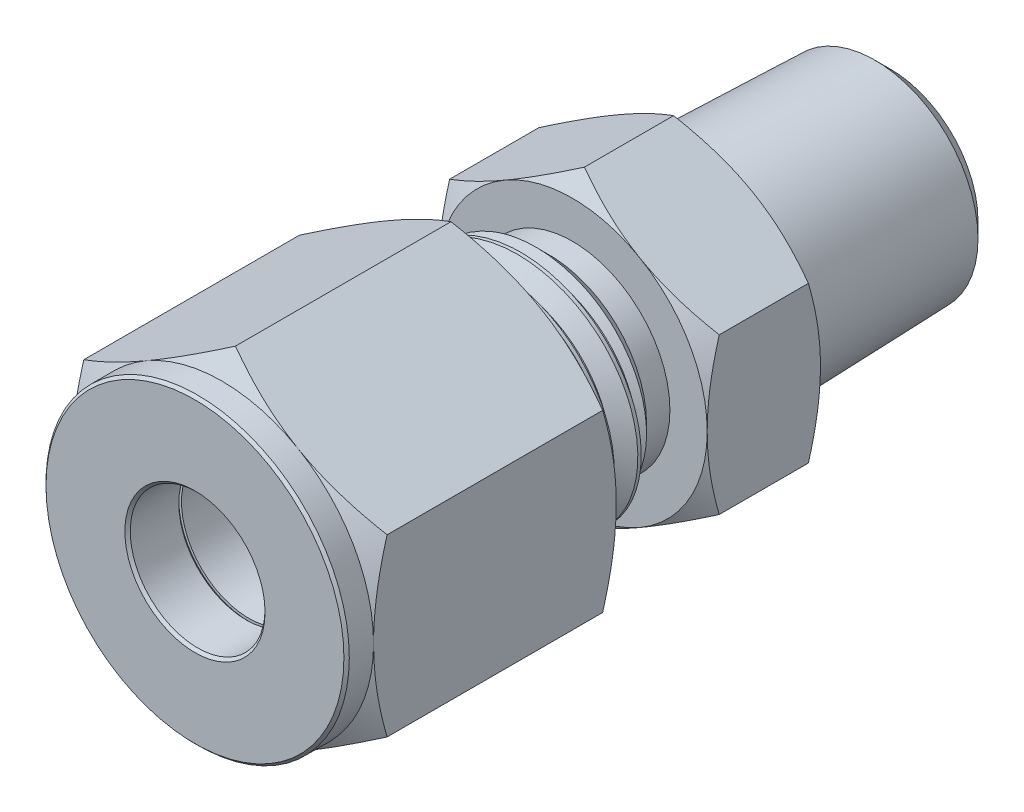
SolidWorks part; units mm, degrees
material "AISI 316 Stainless Steel Sheet (SS)"
ref_plane "Front Plane" through (0, 0, 0) normal (0, 0, 1) x (1, 0, 0)
ref_plane "Top Plane" through (0, 0, 0) normal (0, 1, 0) x (1, 0, 0)
ref_plane "Right Plane" through (0, 0, 0) normal (1, 0, 0) x (0, 0, -1)
sketch "Sketch1" plane through (0, 0, 0) normal (1, 0, 0) x (0, 0, -1)
  line L0 (0, 0) -> (32.766, 0) construction
  line L1 (0, 3.175) -> (0, -3.175) construction
  line L2 (12.7, 7.1437) -> (12.7, -7.1437) construction
  line L3 (5.08, 5.5562) -> (5.08, -5.5562) construction
  line L4 (5.08, 5.5562) -> (5.08, 4.2862) construction
  line L5 (23.114, 6.35) -> (23.114, -6.35) construction
  line L6 (4.445, 4.699) -> (9.3218, 3.6068) construction
  line L7 (9.3218, 3.6068) -> (9.3218, 3.175) construction
  line L8 (9.3218, 3.175) -> (5.1308, 3.175) construction
  line L9 (5.1308, 3.175) -> (4.445, 3.8608) construction
  line L10 (4.445, 3.8608) -> (4.445, 4.699) construction
  line L11 (2.54, 4.6609) -> (3.556, 4.6609) construction
  line L12 (3.556, 4.6609) -> (3.556, 3.8608) construction
  line L13 (3.556, 3.8608) -> (4.445, 3.8608) construction
  line L14 (23.114, 2.3749) -> (23.114, -2.3749) construction
  line L15 (4.445, 3.8608) -> (4.445, 3.175) construction
  line L16 (5.1308, 3.175) -> (2.54, 3.175) construction
  line L17 (2.54, 3.175) -> (2.54, 4.6609) construction
  line L18 (4.445, 3.175) -> (5.1308, 3.175) construction
  line L19 (0, 3.175) -> (2.54, 3.175) construction
  line L20 (2.54, 3.175) -> (5.08, 3.175) construction
  line L21 (32.766, 4.8332) -> (32.766, -4.8332) construction
  line L22 (22.799, 5.1435) -> (22.799, -5.1435) construction
  line L23 (22.799, 5.1435) -> (32.766, 4.8332) construction
  line L24 (22.799, 5.1435) -> (22.799, 4.2028) construction
  line L25 (26.0629, 5.0419) -> (26.0629, -5.0419) construction
  line L26 (32.766, 3.4163) -> (32.766, -3.4163) construction
  point P4 (1.27, 0)
  point P10 (5.08, 0)
  point P12 (12.7, 0)
  point P15 (17.78, 0)
  point P16 (7.366, 0)
  point P17 (15.24, 0)
  point P33 (23.114, 0)
  point P40 (22.799, 0)
  point P44 (26.0629, 0)
  dimension "R" = 9.652
sketch "Sketch2" plane through (0, 0, 0) normal (0, 0, 1) x (1, 0, 0)
  line L0 (0, 3.175) -> (0, -3.175) construction
  line L1 (0, 8.2489) -> (-7.1437, 4.1244)
  line L2 (-7.1437, 4.1244) -> (-7.1438, -4.1244)
  line L3 (-7.1438, -4.1244) -> (0, -8.2489)
  line L4 (0, -8.2489) -> (7.1437, -4.1244)
  line L5 (7.1437, -4.1244) -> (7.1438, 4.1244)
  line L6 (7.1438, 4.1244) -> (0, 8.2489)
  line L7 (0, 8.2489) -> (0, 0) construction
  circle A0 centre (0, 0) radius 7.1438 construction
extrude "Boss-Extrude1" add sketch "Sketch2" against normal up to vertex (12.7 mm away) up to point (0, 0, -12.7)
sketch "Sketch3" plane through (0, 0, 0) normal (1, 0, 0) x (0, 0, -1)
  line L0 (0, 8.2489) -> (0, 7.1437)
  line L1 (0, 4.1244) -> (0, 8.2489) construction
  line L2 (0, 7.1437) -> (1.27, 7.1437)
  line L3 (1.27, 7.1437) -> (1.9081, 8.2489)
  line L4 (12.7, 8.2489) -> (0, 8.2489) construction
  line L5 (1.9081, 8.2489) -> (12.0619, 8.2489)
  line L6 (12.0619, 8.2489) -> (12.7, 7.1437)
  line L7 (12.7, 7.1437) -> (12.7, 8.2489)
  line L8 (12.7, 8.2489) -> (12.7, 9.354)
  line L9 (12.7, 9.354) -> (0, 9.354)
  line L10 (0, 9.354) -> (0, 8.2489)
  line L11 (0, 3.175) -> (0, 0)
  line L12 (0, 3.175) -> (0, -3.175) construction
  line L13 (0, 0) -> (12.7, 0)
  line L14 (12.7, 7.1437) -> (12.7, -7.1437) construction
  line L15 (12.7, 0) -> (12.7, 5.5562)
  line L16 (12.7, 5.5562) -> (5.08, 5.5562)
  line L17 (5.08, 5.5562) -> (5.08, 4.2862) construction
  line L18 (5.08, 4.2862) -> (2.54, 4.2862) construction
  line L19 (2.54, 4.2862) -> (2.54, 3.175)
  line L20 (2.54, 3.175) -> (0, 3.175)
  line L21 (2.54, 4.2862) -> (2.54, 5.5562) construction
  line L22 (2.54, 5.5562) -> (5.08, 5.5562) construction
  line L23 (5.08, 4.9212) -> (2.54, 4.9213)
  line L24 (2.54, 4.9213) -> (2.54, 4.2862)
  line L25 (5.08, 4.9212) -> (5.08, 5.5562)
  dimension "D1" = 30
  dimension "D2" = 1.27
revolve "Cut-Revolve1" cut sketch "Sketch3" angle 360 about L0
chamfer "Chamfer1" distance 0.127 angle 45 3 edges at (3.175, 0, -2.54) (3.175, 0, 0) (7.1437, 0, 0)
sketch "Sketch4" plane through (0, 0, 0) normal (1, 0, 0) x (0, 0, -1)
  line L1 (23.114, 0) -> (7.366, 0)
  line L2 (23.114, 0) -> (23.114, 5.5563)
  line L3 (23.114, 5.5563) -> (7.366, 5.5562)
  line L4 (7.366, 0) -> (7.366, 5.5562)
  dimension "D1" = 15.748
revolve "Revolve1" add sketch "Sketch4" angle 360 about L1
sketch "Sketch5" plane through (0, 0, -7.366) normal (0, 0, -1) x (-1, 0, 0)
  circle A0 centre (0, 0) radius 5.5562 construction
  circle A1 centre (0, 0) radius 5.5562
  point P3 (0, 5.5562)
curve "Helix/Spiral1" pitch 1.27 height 17.018 radius 5.5562 centre (0, 0, -7.366) axis (0, 0, -1) start towards (0, 1, 0)
sketch "Sketch6" plane through (0, 0, 0) normal (1, 0, 0) x (0, 0, -1)
  line L0 (6.1754, 5.6937) -> (7.4454, 5.6937) construction
  line L1 (7.4454, 5.6937) -> (6.8104, 4.5939) construction
  line L2 (6.8104, 4.5939) -> (6.1754, 5.6937) construction
  line L3 (6.731, 4.7314) -> (6.8898, 4.7314) construction
  line L4 (6.2548, 5.5563) -> (7.366, 5.5563) construction
  line L5 (6.8104, 4.5939) -> (6.8104, 4.7314) construction
  line L6 (6.8104, 5.5563) -> (6.8104, 5.6937) construction
  line L7 (6.731, 4.7314) -> (6.2151, 5.625)
  line L8 (6.2151, 5.625) -> (7.4057, 5.625)
  line L9 (7.4057, 5.625) -> (6.8898, 4.7314)
  line L10 (6.8898, 4.7314) -> (6.731, 4.7314)
  point P10 (6.8104, 5.625)
  dimension "D1" = 1.27
  dimension "D2" = 0.1588
sweep "Cut-Sweep1" cut profiles "Sketch6" path "Helix/Spiral1" align with end faces yes
sketch "Sketch7" plane through (0, 0, -23.114) normal (0, 0, -1) x (-1, 0, 0)
  line L0 (0, 0) -> (0, 7.3323) construction
  line L1 (0, 7.3323) -> (-6.35, 3.6662)
  line L2 (-6.35, 3.6662) -> (-6.35, -3.6662)
  line L3 (-6.35, -3.6662) -> (0, -7.3323)
  line L4 (0, -7.3323) -> (6.35, -3.6662)
  line L5 (6.35, -3.6662) -> (6.35, 3.6662)
  line L6 (6.35, 3.6662) -> (0, 7.3323)
  circle A0 centre (0, 0) radius 6.35 construction
extrude "Boss-Extrude2" add sketch "Sketch7" against normal up to vertex (5.334 mm away) up to point (0, 0, -17.78)
sketch "Sketch8" plane through (0, 0, 0) normal (1, 0, 0) x (0, 0, -1)
  line L0 (7.366, 5.6937) -> (7.366, 4.5939)
  line L1 (7.366, 4.5939) -> (8.4659, 5.6937)
  line L2 (8.4659, 5.6937) -> (7.366, 5.6937)
  line L3 (17.78, 5.6937) -> (15.5803, 5.6937)
  line L4 (15.5803, 5.6937) -> (16.6801, 4.5939)
  line L5 (16.6801, 4.5939) -> (17.78, 4.5939)
  line L6 (17.78, 4.5939) -> (17.78, 5.6937)
  line L7 (17.78, 6.35) -> (18.3472, 7.3323)
  line L8 (17.78, 7.3323) -> (17.78, 3.6662) construction
  line L9 (17.78, 7.3323) -> (23.114, 7.3323) construction
  line L10 (18.3472, 7.3323) -> (22.5468, 7.3323)
  line L11 (15.24, 2.3749) -> (23.114, 2.3749)
  line L12 (22.5468, 7.3323) -> (23.114, 6.35)
  line L13 (23.114, -3.6662) -> (23.114, 3.6662) construction
  line L14 (23.114, 7.3323) -> (23.114, 8.3147)
  line L15 (23.114, 8.3147) -> (17.78, 8.3147)
  line L16 (17.78, 8.3147) -> (17.78, 7.3323)
  line L17 (17.78, 7.3323) -> (17.78, 6.35)
  line L18 (6.8104, 4.5939) -> (7.366, 4.5939) construction
  line L19 (7.4454, 5.6937) -> (7.366, 5.6937) construction
  line L20 (8.4659, 5.6937) -> (15.5803, 5.6937) construction
  line L21 (16.6801, 4.5939) -> (7.366, 4.5939) construction
  line L22 (7.366, 4.0448) -> (11.2498, 3.175)
  line L23 (23.114, 6.35) -> (23.114, 7.3323)
  line L24 (7.366, 3.9289) -> (7.366, -4.7433) construction
  line L25 (4.445, 4.699) -> (9.3218, 3.6068) construction
  line L26 (23.114, 0) -> (7.366, 0)
  line L27 (7.366, 0) -> (7.366, 4.0448)
  line L28 (11.2498, 3.175) -> (15.24, 3.175)
  line L29 (15.24, 3.175) -> (15.24, 2.3749)
  line L30 (23.114, 2.3749) -> (23.114, 0)
  line L31 (15.24, 0) -> (15.24, 2.3749) construction
  line L32 (23.114, 6.35) -> (23.114, -6.35) construction
  dimension "D1" = 30
revolve "Cut-Revolve2" cut sketch "Sketch8" angle 360 about L0
sketch "Sketch9" plane through (0, 0, 0) normal (1, 0, 0) x (0, 0, -1)
  line L0 (4.445, 4.699) -> (4.445, 3.8608)
  line L1 (4.445, 3.8608) -> (5.1308, 3.175)
  line L2 (5.1308, 3.175) -> (9.3218, 3.175)
  line L3 (9.3218, 3.175) -> (9.3218, 3.6068)
  line L4 (9.3218, 3.6068) -> (4.445, 4.699)
revolve "Revolve2" add sketch "Sketch9" angle 360 about L0
sketch "Sketch10" plane through (0, 0, 0) normal (1, 0, 0) x (0, 0, -1)
  line L0 (2.54, 4.6609) -> (3.556, 4.6609)
  line L1 (3.556, 4.6609) -> (3.556, 3.8608)
  line L2 (3.556, 3.8608) -> (4.445, 3.8608)
  line L4 (4.445, 3.8608) -> (5.1308, 3.175)
  line L5 (5.1308, 3.175) -> (2.54, 3.175)
  line L6 (2.54, 3.175) -> (2.54, 4.6609)
revolve "Revolve3" add sketch "Sketch10" angle 360 about L0
sketch "Sketch11" plane through (0, 0, 0) normal (1, 0, 0) x (0, 0, -1)
  line L0 (22.799, 0) -> (32.766, 0)
  line L1 (32.766, 0) -> (32.766, 4.8332)
  line L2 (32.766, 4.8332) -> (22.799, 5.1435)
  line L3 (22.799, 5.1435) -> (22.799, 0)
revolve "Revolve4" add sketch "Sketch11" angle 360 about L0
sketch "Sketch12" plane through (0, 0, -32.766) normal (0, 0, -1) x (-1, 0, 0)
  circle A1 centre (0, 0) radius 4.8332
  circle A2 centre (0, 0) radius 4.8332
  point P0 (0, 4.8332)
  dimension "D1" = 0
curve "Helix/Spiral2"
sketch "Sketch13" plane through (0, 0, 0) normal (1, 0, 0) x (0, 0, -1)
  line L0 (32.7072, 4.935) -> (33.6479, 4.935) construction
  line L1 (32.7072, 4.935) -> (33.1776, 4.1203) construction
  line L2 (33.1776, 4.1203) -> (33.6479, 4.935) construction
  line L3 (33.1188, 4.2221) -> (33.2364, 4.2221) construction
  line L4 (32.766, 4.8332) -> (33.5891, 4.8332) construction
  line L5 (33.1776, 4.1203) -> (33.1776, 4.2221) construction
  line L6 (33.1776, 4.8332) -> (33.1776, 4.935) construction
  line L7 (33.1776, 4.8841) -> (33.6185, 4.8841) construction
  line L8 (33.1776, 4.1203) -> (33.1776, -4.8204) construction
  line L9 (33.1776, -4.8204) -> (32.2373, -4.8496) construction
  line L10 (32.2373, -4.8496) -> (31.297, -4.8789) construction
  line L11 (31.297, -4.8789) -> (30.3567, -4.9082) construction
  line L12 (32.7072, 4.935) -> (33.6185, 4.8841)
  line L13 (33.6185, 4.8841) -> (33.2364, 4.2221)
  line L14 (33.2364, 4.2221) -> (33.1188, 4.2221)
  line L15 (33.1188, 4.2221) -> (32.7072, 4.935)
  line L16 (22.799, -5.1435) -> (32.766, -4.8332) construction
  line L17 (30.3567, -4.9082) -> (29.4164, -4.9375) construction
  line L18 (29.4164, -4.9375) -> (28.4761, -4.9667) construction
  dimension "D1" = 0.9407
  dimension "D2" = 0.1176
sweep "Cut-Sweep2" [suppressed] cut profiles "Sketch13" path "Helix/Spiral2"
combine bodies "Combine1" operation type add bodies to combine 113 121
sketch "Sketch14" plane through (0, 0, 0) normal (1, 0, 0) x (0, 0, -1)
  line L0 (33.1776, 4.1203) -> (32.766, 4.1203) construction
  line L5 (32.766, 4.8332) -> (32.766, -4.8332) construction
  line L6 (32.766, 4.1203) -> (31.9513, 4.935)
  line L7 (31.9513, 4.935) -> (32.766, 4.935)
  line L8 (32.766, 4.935) -> (32.766, 4.1203)
  line L9 (32.7072, 4.935) -> (33.6479, 4.935) construction
  line L10 (32.766, 3.4163) -> (22.799, 3.4163)
  line L11 (22.799, 3.4163) -> (22.799, 0) construction
  line L12 (20.7463, 0) -> (32.766, 0)
  line L13 (20.7463, 0) -> (22.799, 3.4163)
  line L14 (32.766, 0) -> (32.766, 3.4163)
  dimension "D1" = 59
revolve "Cut-Revolve4" cut sketch "Sketch14" angle 360 about L0
equation "\"D4@Helix/Spiral1\" = \"Straight Thread Pitch@Sketch1\""
equation "\"D3@Helix/Spiral1\" = \"D4@Helix/Spiral1\" + \"D1@Sketch4\""
equation "\"D1@Sketch6\" = \"D4@Helix/Spiral1\""
equation "\"D2@Sketch6\" = \"D1@Sketch6\" / 8"
equation "\"D4@Helix/Spiral2\" = \"Pipe Pitch@Sketch1\""
equation "\"D3@Helix/Spiral2\" = \"D4@Helix/Spiral2\" + \"L4@Sketch1\""
equation "\"D1@Sketch13\" = \"D4@Helix/Spiral2\""
equation "\"D2@Sketch13\" = \"D1@Sketch13\" / 8"
